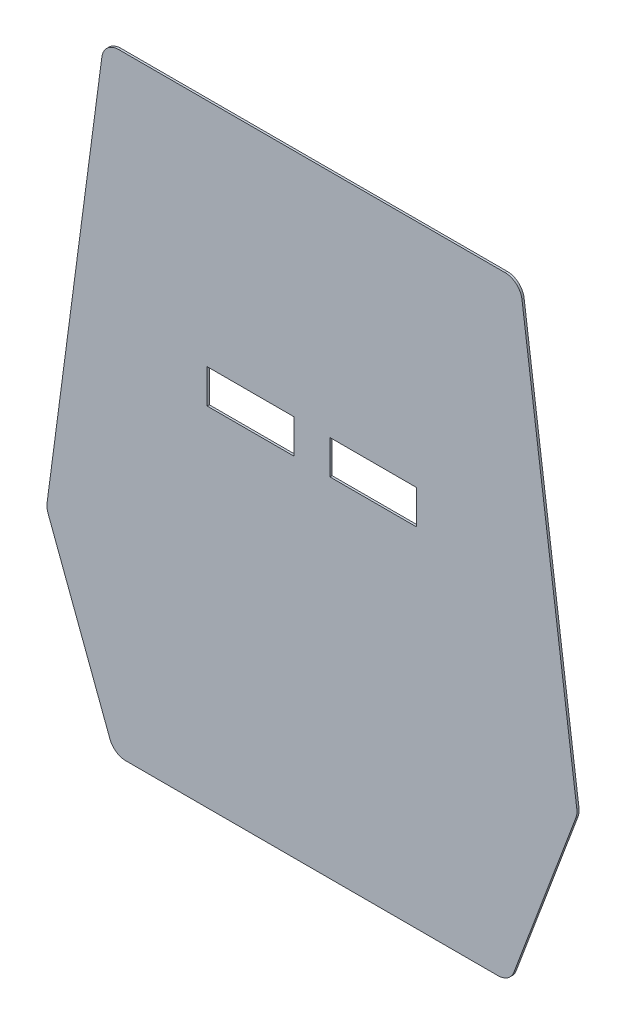
SolidWorks part; units mm, degrees
ref_plane "Front Plane" through (0, 0, 0) normal (0, 0, 1) x (1, 0, 0)
ref_plane "Top Plane" through (0, 0, 0) normal (0, 1, 0) x (1, 0, 0)
ref_plane "Right Plane" through (0, 0, 0) normal (1, 0, 0) x (0, 0, -1)
sketch "Sketch1" plane through (0, 0, 0) normal (0, 0, 1) x (1, 0, 0)
  line L4 (-305.02, 897.72) -> (-389.09, 263.21)
  line L5 (-389.09, 263.21) -> (-290.03, 0)
  line L6 (290.03, 0) -> (-290.03, 0)
  line L7 (-305.02, 897.72) -> (305.02, 897.72)
  line L8 (0, 897.72) -> (0, 0) construction
  line L9 (389.09, 263.21) -> (290.03, 0)
  line L10 (305.02, 897.72) -> (389.09, 263.21)
  dimension "D1" = 263.21
  dimension "D3" = 778.18
  dimension "D4" = 610.04
  dimension "D2" = 580.06
  dimension "D5" = 897.72
base flange "Base-Flange1" sketch "Sketch1" thickness 3.175 reverse thickness direction no parameters "D1"=0.7366
fillet "Fillet1" radius 25 6 edges at (-389.09, 263.21, -1.5875) (-290.03, 0, -1.5875) (290.03, 0, -1.5875) (389.09, 263.21, -1.5875) (305.02, 897.72, -1.5875) (-305.02, 897.72, -1.5875)
sketch "Sketch2" plane through (0, 0, 0) normal (0, 0, 1) x (1, 0, 0)
  line L0 (-272.7269, 0) -> (272.7269, 0) construction
  line L1 (-153.5, 560) -> (-26.5, 560)
  line L2 (-153.5, 560) -> (-153.5, 510)
  line L3 (-153.5, 510) -> (-26.5, 510)
  line L4 (-26.5, 560) -> (-26.5, 510)
  line L5 (-153.5, 560) -> (-26.5, 510) construction
  line L6 (-153.5, 510) -> (-26.5, 560) construction
  line L7 (26.5, 560) -> (153.5, 560)
  line L8 (26.5, 560) -> (26.5, 510)
  line L9 (26.5, 510) -> (153.5, 510)
  line L10 (153.5, 560) -> (153.5, 510)
  line L11 (26.5, 560) -> (153.5, 510) construction
  line L12 (26.5, 510) -> (153.5, 560) construction
  point P0 (-90, 535)
  point P5 (90, 535)
  point P13 (0, 0)
  dimension "D1" = 50
  dimension "D2" = 50
  dimension "D3" = 90
  dimension "D4" = 90
  dimension "D5" = 127
  dimension "D6" = 127
  dimension "D7" = 535
extrude "Cut-Extrude1" cut sketch "Sketch2" against normal blind 10 normal cut yes
sketch "Sketch3" plane through (0, 0, -3.175) normal (0, 0, -1) x (-1, 0, 0)
  line L0 (0, 897.72) -> (0, 0) construction
  line L1 (-50, 735) -> (50, 735)
  line L2 (-50, 735) -> (-50, 635)
  line L3 (-50, 635) -> (50, 635)
  line L4 (50, 735) -> (50, 635)
  line L5 (-50, 735) -> (50, 635) construction
  line L6 (-50, 635) -> (50, 735) construction
  line L7 (26.5, 560) -> (153.5, 560) construction
  point P0 (0, 685)
  dimension "D1" = 100
  dimension "D2" = 100
  dimension "D3" = 125
extrude "Boss-Extrude1" add sketch "Sketch3" along normal blind 2
sketch "Sketch4" plane through (0, 0, -5.175) normal (0, 0, -1) x (-1, 0, 0)
  line L0 (50, 735) -> (-50, 735) construction
  line L1 (-45, 730) -> (45, 730)
  line L2 (-45, 730) -> (-45, 640)
  line L3 (-45, 640) -> (45, 640)
  line L4 (45, 730) -> (45, 640)
  line L5 (-45, 730) -> (45, 640) construction
  line L6 (-45, 640) -> (45, 730) construction
  line L7 (-50, 735) -> (-50, 635) construction
  point P0 (0, 685)
  dimension "D1" = 90
  dimension "D2" = 90
  dimension "D3" = 5
  dimension "D4" = 5
extrude "Boss-Extrude2" add sketch "Sketch4" along normal blind 40
fillet "Fillet3" radius 20 4 edges at (45, 685, -45.175) (0, 640, -45.175) (-45, 685, -45.175) (0, 730, -45.175)
sketch "Bend-Lines1" [suppressed] plane through (0, 0, 0) normal (0, 1, 0) x (1, 0, 0)
sketch "Bounding-Box1" [suppressed] plane through (0, 0, 0) normal (0, 1, 0) x (1, 0, 0)
sheet metal parameters "Sheet-Metal1" thickness 3.175 parameters "D1"=0.7366
flat pattern "Flat-Pattern1" [suppressed]
sketch "Bend-Lines2" plane through (0, 0, 0) normal (0, 1, 0) x (1, 0, 0)
sketch3d "Bounding-Box2" [suppressed]
  line L0 (388.4827, 897.72, 0) -> (388.4827, 0, 0) construction
  line L1 (-388.4827, 897.72, 0) -> (-388.4827, 0, 0) construction
  line L2 (388.4827, 897.72, 0) -> (-388.4827, 897.72, 0) construction
  line L3 (388.4827, 0, 0) -> (-388.4827, 0, 0) construction
sheet metal parameters "Sheet-Metal2" thickness 3.175 parameters "D1"=0.7366
flat pattern "Flat-Pattern1"
sketch "Bend-Lines2" plane through (0, 0, 0) normal (0, 1, 0) x (1, 0, 0)
sketch3d "Bounding-Box2" [suppressed]
  line L0 (388.4827, 897.72, 0) -> (388.4827, 0, 0) construction
  line L1 (-388.4827, 897.72, 0) -> (-388.4827, 0, 0) construction
  line L2 (388.4827, 897.72, 0) -> (-388.4827, 897.72, 0) construction
  line L3 (388.4827, 0, 0) -> (-388.4827, 0, 0) construction
sheet metal parameters "Sheet-Metal3" thickness 3.175 parameters "D1"=0.7366
flat pattern "Flat-Pattern1"
sketch "Bend-Lines2" plane through (0, 0, 0) normal (0, 1, 0) x (1, 0, 0)
sketch3d "Bounding-Box2" [suppressed]
  line L0 (388.4827, 897.72, 0) -> (388.4827, 0, 0) construction
  line L1 (-388.4827, 897.72, 0) -> (-388.4827, 0, 0) construction
  line L2 (388.4827, 897.72, 0) -> (-388.4827, 897.72, 0) construction
  line L3 (388.4827, 0, 0) -> (-388.4827, 0, 0) construction
sheet metal parameters "Sheet-Metal4" thickness 3.175 parameters "D1"=0.7366
flat pattern "Flat-Pattern1"
sketch "Bend-Lines2" plane through (0, 0, 0) normal (0, 1, 0) x (1, 0, 0)
sketch3d "Bounding-Box2" [suppressed]
  line L0 (388.4827, 897.72, 0) -> (388.4827, 0, 0) construction
  line L1 (-388.4827, 897.72, 0) -> (-388.4827, 0, 0) construction
  line L2 (388.4827, 897.72, 0) -> (-388.4827, 897.72, 0) construction
  line L3 (388.4827, 0, 0) -> (-388.4827, 0, 0) construction
equation "\"D1@Sketch1\"=275.71-12.5"
equation "\"D5@Sketch1\"=910.22-12.5"
